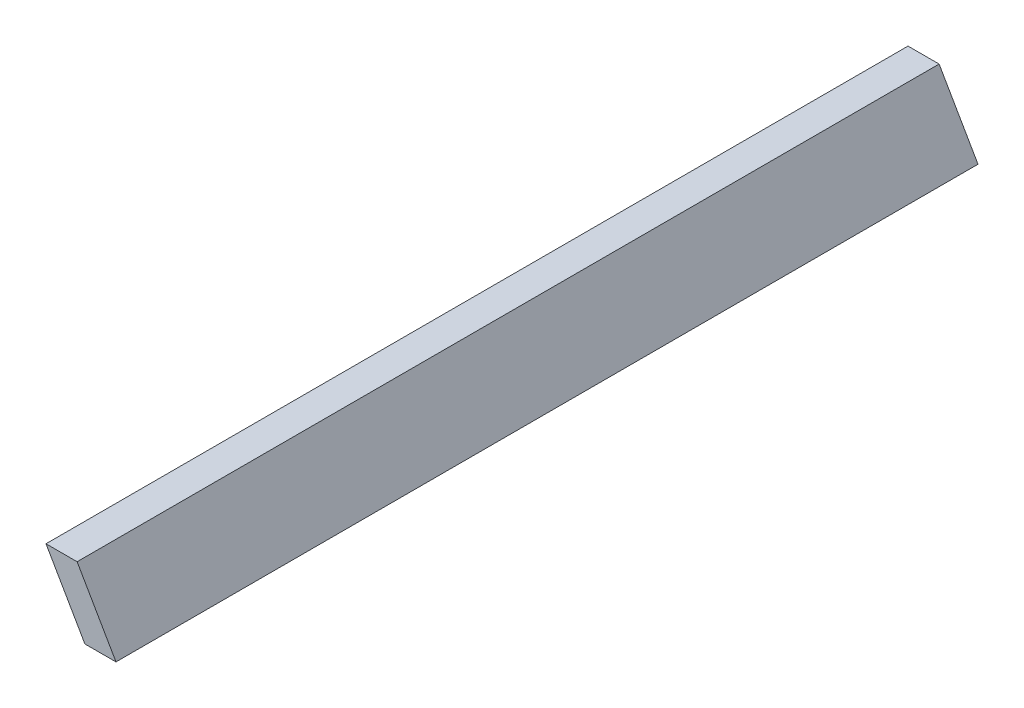
SolidWorks part; units mm, degrees
material "Gray Cast Iron"
ref_plane "Front Plane" through (0, 0, 0) normal (0, 0, 1) x (1, 0, 0)
ref_plane "Top Plane" through (0, 0, 0) normal (0, 1, 0) x (1, 0, 0)
ref_plane "Right Plane" through (0, 0, 0) normal (1, 0, 0) x (0, 0, -1)
sketch "Sketch6" plane through (0, 0, 0) normal (0, 0, 1) x (1, 0, 0)
  line B0 (-32.3728, -15.875) -> (94.6272, -15.875)
  line B1 (94.6272, 0) -> (69.5868, 0)
  line B2 (-9.1654, 15.875) -> (0, 0)
  line B3 (0, 0) -> (-32.3728, 0)
  line B4 (-7.3323, 0) -> (-16.4978, 15.875)
  line B5 (-16.4978, 15.875) -> (-9.1654, 15.875)
  line B6 (15.0709, 15.875) -> (15.0709, -3.175)
  line B7 (15.0709, -3.175) -> (47.1836, -3.175)
  line B8 (47.1836, -3.175) -> (47.1836, 15.875)
  line B9 (15.0709, 15.875) -> (-9.1654, 15.875)
  line B10 (-32.3728, 0) -> (-32.3728, 31.75)
  line B11 (-32.3728, 31.75) -> (94.6272, 31.75)
  line B12 (94.6272, 31.75) -> (94.6272, 0)
  line B13 (31.1272, 31.75) -> (31.1272, -15.875) construction
  line B14 (-7.3323, 0) -> (69.5868, 0) construction
  line B15 (2.4252, 21.082) -> (59.8292, 21.082) construction
  line B16 (5.7272, -8.001) -> (56.5272, -8.001) construction
  line B17 (5.7272, -8.001) -> (5.7272, 7.9375) construction
  line B18 (56.5272, -8.001) -> (56.5272, 7.9375) construction
  line B19 (-21.7048, 7.9375) -> (83.9592, 7.9375) construction
  circle B20 centre (31.1272, 6.35) radius 18.669 construction
sketch_block_instance "dovetail pair-1"
sketch_block "dovetail pair" parameters "D8"=37.338, "D1"=60, "D2"=127, "D3"=6.35, "D4"=15.875, "D5"=31.75, "D6"=95.25, "D7"=19.05, "D9"=60, "D10"=31.75, "D11"=50.8, "D12"=23.876, "D13"=7.874, "D14"=10.668, "D15"=34.798, "D16"=21.082, "D17"=7.9375
sketch "end-profile" plane through (0, 0, 0) normal (0, 0, 1) x (1, 0, 0)
  line L0 (0, 0) -> (-7.3323, 0)
  line L4 (-9.1654, 15.875) -> (0, 0) construction
  line L5 (-16.4978, 15.875) -> (-9.1654, 15.875) construction
  line L6 (-7.3323, 0) -> (-16.4978, 15.875) construction
  line L7 (-9.1654, 15.875) -> (0, 0)
  line L8 (-16.4978, 15.875) -> (-9.1654, 15.875)
  line L9 (-7.3323, 0) -> (-16.4978, 15.875)
extrude "Boss-Extrude1" add sketch "end-profile" along normal blind 203.2
ref_plane "screw pocket Plane1" through (-16.4978, 0, 0) normal (1, 0, 0) x (0, 0, -1)
sketch "Sketch4" plane through (-16.4978, 0, 0) normal (1, 0, 0) x (0, 0, -1)
  line L0 (0, 7.9375) -> (-203.2, 7.9375) construction
  line L1 (-203.2, 15.875) -> (-203.2, 0) construction
  line L3 (-181.1871, 7.9375) -> (-181.1871, 0)
  line L4 (-181.1871, 0) -> (-174.4129, 0)
  line L5 (-174.4129, 0) -> (-174.4129, 7.9375)
  line L6 (-143.0871, 7.9375) -> (-143.0871, 0)
  line L7 (-143.0871, 0) -> (-136.3129, 0)
  line L8 (-136.3129, 0) -> (-136.3129, 7.9375)
  line L9 (-104.9871, 7.9375) -> (-104.9871, 0)
  line L10 (-104.9871, 0) -> (-98.2129, 0)
  line L11 (-98.2129, 0) -> (-98.2129, 7.9375)
  line L12 (-66.8871, 7.9375) -> (-66.8871, 0)
  line L13 (-66.8871, 0) -> (-60.1129, 0)
  line L14 (-60.1129, 0) -> (-60.1129, 7.9375)
  line L15 (-28.7871, 7.9375) -> (-28.7871, 0)
  line L16 (-28.7871, 0) -> (-22.0129, 0)
  line L17 (-22.0129, 0) -> (-22.0129, 7.9375)
  line L18 (-181.1871, 7.9375) -> (-143.0871, 7.9375) construction
  line L19 (-203.2, 0) -> (0, 0) construction
  line L21 (0, 0) -> (0, 15.875) construction
  arc A0 (-174.4129, 7.9375) -> (-181.1871, 7.9375) centre (-177.8, 7.9375) ccw
  arc A1 (-136.3129, 7.9375) -> (-143.0871, 7.9375) centre (-139.7, 7.9375) ccw
  arc A2 (-98.2129, 7.9375) -> (-104.9871, 7.9375) centre (-101.6, 7.9375) ccw
  arc A3 (-60.1129, 7.9375) -> (-66.8871, 7.9375) centre (-63.5, 7.9375) ccw
  arc A4 (-22.0129, 7.9375) -> (-28.7871, 7.9375) centre (-25.4, 7.9375) ccw
  dimension "D1" = 6.7742
  dimension "D2" = 38.1
  dimension "D3" = 5
extrude "Cut-Extrude1" cut sketch "Sketch4" along normal blind 7.112
sketch "Sketch5" [suppressed] plane through (-16.4978, 0, 0) normal (1, 0, 0) x (0, 0, -1)
  line L0 (0, 7.9375) -> (-127, 7.9375) construction
  line L3 (-104.9871, 7.9375) -> (-104.9871, 0)
  line L5 (-104.9871, 0) -> (-98.2129, 0)
  line L6 (-98.2129, 0) -> (-98.2129, 7.9375)
  line L7 (-66.8871, 7.9375) -> (-66.8871, 0)
  line L8 (-66.8871, 0) -> (-60.1129, 0)
  line L9 (-60.1129, 0) -> (-60.1129, 7.9375)
  line L10 (-28.7871, 7.9375) -> (-28.7871, 0)
  line L11 (-28.7871, 0) -> (-22.0129, 0)
  line L12 (-22.0129, 0) -> (-22.0129, 7.9375)
  line L13 (-104.9871, 7.9375) -> (-66.8871, 7.9375) construction
  line L14 (-127, 0) -> (-127, 15.875) construction
  line L15 (-127, 0) -> (0, 0) construction
  line L16 (0, 0) -> (0, 15.875) construction
  arc A0 (-98.2129, 7.9375) -> (-104.9871, 7.9375) centre (-101.6, 7.9375) ccw
  arc A1 (-60.1129, 7.9375) -> (-66.8871, 7.9375) centre (-63.5, 7.9375) ccw
  arc A2 (-22.0129, 7.9375) -> (-28.7871, 7.9375) centre (-25.4, 7.9375) ccw
  dimension "D1" = 6.7742
  dimension "D2" = 38.1
extrude "Cut-Extrude2" [suppressed] cut sketch "Sketch5" along normal blind 7.112
equation "\"dovetail-angle\" = 60"
equation "\"dovetail-stock-width\" = 5"
equation "\"dovetail-stock-height\" = 1.25"
equation "\"dovetail-depth\" = 0.5 * \"dovetail-stock-height\""
equation "\"dovetail-throat-width\" = \"dovetail-stock-width\" - (2 * \"dovetail-depth\")"
equation "\"delta-x\" = 6"
equation "\"delta-y\" = 3"
equation "\"delta-z\"= 2.5"
equation "\"acme-nut-height\"= 0.5"
equation "\"acme-nut-width\"= 0.75"
equation "\"gib-thickness\" = 0.25"
equation "\"x-slide-length\" = \"dovetail-stock-width\" + \"delta-x\""
equation "\"y-slide-length\" = \"dovetail-stock-width\" + \"delta-y\""
equation "\"dog-point-diam\" = .149"
equation "\"dog-point-length\" = .067"
equation "\"dovetail-double-height\" = 2 * \"dovetail-depth\" + 0.5"
equation "\"acme-major-diam\" = .5"
equation "\"acme-pitch-diam\" = 0.45"
equation "\"acme-minor-diam\" = 0.4"
equation "\"acme-nut-od\" = 1.47"
equation "\"acme-nut-length\" = 1"
equation "\"acme-nut-trim-height\" = .75"
equation "\"screw-bearing-od\" = 0.5"
equation "\"screw-bearing-length\" = .375"
equation "\"screw-bearing-id\" = .375"
equation "\"end-plate-thickness\" = \"screw-bearing-length\""
equation "\"screw-add-length\" = 2 * \"end-plate-thickness\" + 1 + 0.5"
equation "\"x-screw-length\" = \"x-slide-length\" + \"screw-add-length\""
equation "\"y-screw-length\" = \"y-slide-length\" + \"screw-add-length\""
equation "\"acme-nut-mount-hole-space-horz\" = 0.95"
equation "\"acme-nut-mount-hole-space-vert\" = 0.5 * \"acme-nut-length\""
equation "\"vise-hole-center-dist\" = 6.75"
equation "\"wiper_plate_clearance\" = .03"
equation "\"dial-width\" = 0.5"
equation "\"quarter-twenty-free-fit\" = .2667"
equation "\"D1@Sketch4\"=\"quarter-twenty-free-fit\""
equation "\"D1@Sketch5\"=\"quarter-twenty-free-fit\""
equation "\"D2@dovetail pair\"=\"dovetail-stock-width\""
equation "\"D1@dovetail pair\"=\"dovetail-angle\""
equation "\"D3@dovetail pair\"=\"gib-thickness\""
equation "\"D4@dovetail pair\"=\"dovetail-depth\""
equation "\"D5@dovetail pair\"=\"dovetail-stock-height\""
equation "\"D6@dovetail pair\"=\"dovetail-throat-width\""
equation "\"D10@dovetail pair\"=\"dovetail-stock-height\""
equation "\"D7@dovetail pair\"=\"acme-nut-trim-height\""
equation "\"D8@dovetail pair\"=\"acme-nut-od\""
equation "\"D9@dovetail pair\"=\"dovetail-angle\""
equation "\"D17@dovetail pair\"=\"dovetail-depth\"/2"
equation "\"acme-nut-trim-width\" = 1.25"
equation "\"acme_nut_clearance\" = .01"
equation "\"dovetail_male_clearance\" = .01"
